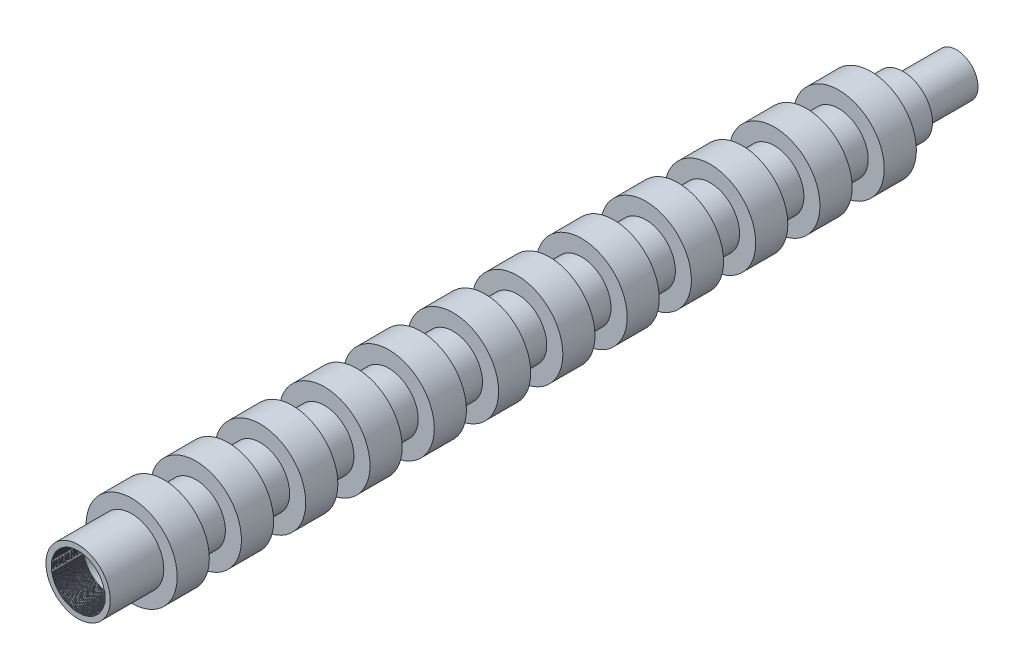
SolidWorks part; units mm, degrees
ref_plane "Front Plane" through (0, 0, 0) normal (0, 0, 1) x (1, 0, 0)
ref_plane "Top Plane" through (0, 0, 0) normal (0, 1, 0) x (1, 0, 0)
ref_plane "Right Plane" through (0, 0, 0) normal (1, 0, 0) x (0, 0, -1)
sketch "Sketch1" plane through (0, 0, 0) normal (0, 0, 1) x (1, 0, 0)
  circle A0 centre (0, 0) radius 6
  circle A1 centre (0, 0) radius 8.5
  dimension "D1" = 12
  dimension "D2" = 17
extrude "Boss-Extrude1" add sketch "Sketch1" along normal blind 10 contours A0 region at (0, 0, 0)
extrude "Boss-Extrude2" add sketch "Sketch1<3>" against normal blind 144 separate body contours A1 A0 | A0 region at (-8.2596, 0, 0)
sketch "Sketch1<3>" plane through (0, 0, 0) normal (0, 0, 1) x (1, 0, 0) same geometry as "Sketch1"
sketch "Sketch3" plane through (0, 0, 0) normal (0, 0, 1) x (1, 0, 0)
  circle A1 centre (0, 0) radius 8.5 construction
  circle A2 centre (0, 0) radius 8.5
sketch "Sketch4" plane through (0, 0, 0) normal (1, 0, 0) x (0, 0, -1)
  line L1 (6, 11.5) -> (12, 11.5)
  line L3 (6, 5.5) -> (12, 5.5)
  line L4 (12, 11.5) -> (12, 5.5)
  line L6 (6, 8.5) -> (12, 8.5) construction
  line L9 (6, 11.5) -> (6, 5.5)
  line L10 (0, 8.5) -> (0, -8.5) construction
  dimension "D1" = 6
  dimension "D2" = 6
  dimension "D3" = 6
sweep "Cut-Sweep1" cut profiles "Sketch4" path "Sketch3"
pattern_linear "LPattern1" count 12 spacing 12 along (0, 0, -1) of "Cut-Sweep1"
sketch "Sketch7" plane through (0, 0, 10) normal (0, 0, 1) x (1, 0, 0)
  line L1 (-5, 1) -> (5, 1)
  line L2 (-5, 1) -> (-5, -1)
  line L3 (-5, -1) -> (5, -1)
  line L4 (5, 1) -> (5, -1)
  line L5 (-5, 1) -> (5, -1) construction
  line L6 (-5, -1) -> (5, 1) construction
  circle A0 centre (0, 0) radius 5
  circle A3 centre (0, 0) radius 6 construction
  dimension "D1" = 10
  dimension "D2" = 1
  dimension "D3" = 2
extrude "Cut-Extrude1" cut sketch "Sketch7" against normal blind 10 contours L3 A0 | L1 A0 L3 | L1 A0 | L4 L3 L2 L1 region at (0, 2.6718, 10) region at (0, 0, 10) region at (0, -2.6718, 10)
sketch "Sketch10" plane through (0, 0, 10) normal (0, 0, 1) x (1, 0, 0)
  circle A0 centre (0, 0) radius 5
  dimension "D1" = 10
curve "Helix/Spiral2" pitch 0.225 height 6 radius 5 centre (0, 0, 10) axis (0, 0, -1) start towards (1, 0, 0)
sketch "Sketch12" plane through (0, 0, 0) normal (1, 0, 0) x (0, 0, -1)
  circle A0 centre (-9.9438, -5) radius 0.05
  spline S0 degree 3 poles (-10, 0) (-9.9953, -0.6513) (-9.9859, -1.9682) (-9.9718, -3.6318) (-9.9577, -4.7438) (-9.9437, -5.1305) (-9.9296, -4.734) (-9.9155, -3.6145) (-9.9014, -1.943) (-9.8873, 0.0252) (-9.8732, 1.9896) (-9.8592, 3.6501) (-9.8451, 4.7532) (-9.831, 5.1304) (-9.8169, 4.7242) (-9.8028, 3.5965) (-9.7887, 1.9196) (-9.7746, -0.0504) (-9.7606, -2.0128) (-9.7465, -3.6678) (-9.7324, -4.7626) (-9.7183, -5.1302) (-9.7042, -4.7143) (-9.6901, -3.5785) (-9.6761, -1.8962) (-9.662, 0.0757) (-9.6479, 2.036) (-9.6338, 3.6854) (-9.6197, 4.772) (-9.6056, 5.1298) (-9.5915, 4.7043) (-9.5775, 3.5604) (-9.5634, 1.8727) (-9.5493, -0.1009) (-9.5352, -2.0591) (-9.5211, -3.7029) (-9.507, -4.7812) (-9.493, -5.1293) (-9.4789, -4.6942) (-9.4648, -3.5422) (-9.4507, -1.8492) (-9.4366, 0.1261) (-9.4225, 2.0822) (-9.4085, 3.7203) (-9.3944, 4.7903) (-9.3803, 5.1287) (-9.3662, 4.6839) (-9.3521, 3.5239) (-9.338, 1.8257) (-9.3239, -0.1513) (-9.3099, -2.1052) (-9.2958, -3.7376) (-9.2817, -4.7992) (-9.2676, -5.128) (-9.2535, -4.6736) (-9.2394, -3.5055) (-9.2254, -1.8021) (-9.2113, 0.1765) (-9.1972, 2.1282) (-9.1831, 3.7549) (-9.169, 4.8081) (-9.1549, 5.1271) (-9.1408, 4.6631) (-9.1268, 3.487) (-9.1127, 1.7784) (-9.0986, -0.2017) (-9.0845, -2.1511) (-9.0704, -3.772) (-9.0563, -4.8168) (-9.0423, -5.1261) (-9.0282, -4.6525) (-9.0141, -3.4685) (-9, -1.7548) (-8.9859, 0.2269) (-8.9718, 2.174) (-8.9577, 3.789) (-8.9437, 4.8255) (-8.9296, 5.125) (-8.9155, 4.6419) (-8.9014, 3.4499) (-8.8873, 1.731) (-8.8732, -0.2521) (-8.8592, -2.1968) (-8.8451, -3.806) (-8.831, -4.834) (-8.8169, -5.1237) (-8.8028, -4.6311) (-8.7887, -3.4312) (-8.7746, -1.7073) (-8.7606, 0.2773) (-8.7465, 2.2196) (-8.7324, 3.8229) (-8.7183, 4.8424) (-8.7042, 5.1224) (-8.6901, 4.6201) (-8.6761, 3.4124) (-8.662, 1.6835) (-8.6479, -0.3025) (-8.6338, -2.2423) (-8.6197, -3.8397) (-8.6056, -4.8507) (-8.5915, -5.1209) (-8.5775, -4.6091) (-8.5634, -3.3935) (-8.5493, -1.6596) (-8.5352, 0.3277) (-8.5211, 2.265) (-8.507, 3.8563) (-8.493, 4.8588) (-8.4789, 5.1193) (-8.4648, 4.598) (-8.4507, 3.3745) (-8.4366, 1.6357) (-8.4225, -0.3529) (-8.4085, -2.2876) (-8.3944, -3.8729) (-8.3803, -4.8669) (-8.3662, -5.1176) (-8.3521, -4.5867) (-8.338, -3.3555) (-8.3239, -1.6118) (-8.3099, 0.378) (-8.2958, 2.3101) (-8.2817, 3.8894) (-8.2676, 4.8748) (-8.2535, 5.1157) (-8.2394, 4.5754) (-8.2254, 3.3364) (-8.2113, 1.5878) (-8.1972, -0.4032) (-8.1831, -2.3326) (-8.169, -3.9058) (-8.1549, -4.8826) (-8.1408, -5.1137) (-8.1268, -4.5639) (-8.1127, -3.3172) (-8.0986, -1.5638) (-8.0845, 0.4283) (-8.0704, 2.355) (-8.0563, 3.9221) (-8.0423, 4.8903) (-8.0282, 5.1116) (-8.0141, 4.5523) (-8, 3.2979) (-7.9859, 1.5398) (-7.9718, -0.4534) (-7.9577, -2.3774) (-7.9437, -3.9383) (-7.9296, -4.8978) (-7.9155, -5.1094) (-7.9014, -4.5406) (-7.8873, -3.2785) (-7.8732, -1.5157) (-7.8592, 0.4786) (-7.8451, 2.3997) (-7.831, 3.9545) (-7.8169, 4.9053) (-7.8028, 5.107) (-7.7887, 4.5289) (-7.7746, 3.2591) (-7.7606, 1.4916) (-7.7465, -0.5037) (-7.7324, -2.422) (-7.7183, -3.9705) (-7.7042, -4.9126) (-7.6901, -5.1045) (-7.6761, -4.5169) (-7.662, -3.2396) (-7.6479, -1.4674) (-7.6338, 0.5288) (-7.6197, 2.4442) (-7.6056, 3.9864) (-7.5915, 4.9198) (-7.5775, 5.1019) (-7.5634, 4.5049) (-7.5493, 3.22) (-7.5352, 1.4433) (-7.5211, -0.5538) (-7.507, -2.4664) (-7.493, -4.0022) (-7.4789, -4.9269) (-7.4648, -5.0992) (-7.4507, -4.4928) (-7.4366, -3.2003) (-7.4225, -1.419) (-7.4085, 0.5789) (-7.3944, 2.4885) (-7.3803, 4.018) (-7.3662, 4.9339) (-7.3521, 5.0964) (-7.338, 4.4806) (-7.3239, 3.1805) (-7.3099, 1.3948) (-7.2958, -0.604) (-7.2817, -2.5105) (-7.2676, -4.0336) (-7.2535, -4.9408) (-7.2394, -5.0934) (-7.2254, -4.4682) (-7.2113, -3.1607) (-7.1972, -1.3705) (-7.1831, 0.629) (-7.169, 2.5325) (-7.1549, 4.0492) (-7.1408, 4.9475) (-7.1268, 5.0903) (-7.1127, 4.4558) (-7.0986, 3.1408) (-7.0845, 1.3462) (-7.0704, -0.654) (-7.0563, -2.5544) (-7.0423, -4.0646) (-7.0282, -4.9541) (-7.0141, -5.0871) (-7, -4.4432) (-6.9859, -3.1208) (-6.9718, -1.3218) (-6.9577, 0.6791) (-6.9437, 2.5762) (-6.9296, 4.0799) (-6.9155, 4.9606) (-6.9014, 5.0838) (-6.8873, 4.4305) (-6.8732, 3.1007) (-6.8592, 1.2974) (-6.8451, -0.704) (-6.831, -2.598) (-6.8169, -4.0952) (-6.8028, -4.967) (-6.7887, -5.0803) (-6.7746, -4.4178) (-6.7606, -3.0806) (-6.7465, -1.273) (-6.7324, 0.729) (-6.7183, 2.6197) (-6.7042, 4.1103) (-6.6901, 4.9733) (-6.6761, 5.0767) (-6.662, 4.4049) (-6.6479, 3.0604) (-6.6338, 1.2485) (-6.6197, -0.754) (-6.6056, -2.6414) (-6.5915, -4.1254) (-6.5775, -4.9794) (-6.5634, -5.073) (-6.5493, -4.3919) (-6.5352, -3.0401) (-6.5211, -1.2241) (-6.507, 0.7789) (-6.493, 2.663) (-6.4789, 4.1403) (-6.4648, 4.9854) (-6.4507, 5.0692) (-6.4366, 4.3788) (-6.4225, 3.0198) (-6.4085, 1.1996) (-6.3944, -0.8038) (-6.3803, -2.6845) (-6.3662, -4.1552) (-6.3521, -4.9913) (-6.338, -5.0652) (-6.3239, -4.3656) (-6.3099, -2.9993) (-6.2958, -1.175) (-6.2817, 0.8287) (-6.2676, 2.7059) (-6.2535, 4.1699) (-6.2394, 4.9971) (-6.2254, 5.0612) (-6.2113, 4.3523) (-6.1972, 2.9788) (-6.1831, 1.1504) (-6.169, -0.8536) (-6.1549, -2.7273) (-6.1408, -4.1846) (-6.1268, -5.0027) (-6.1127, -5.057) (-6.0986, -4.3389) (-6.0845, -2.9583) (-6.0704, -1.1258) (-6.0563, 0.8785) (-6.0423, 2.7487) (-6.0282, 4.1991) (-6.0141, 5.0083) (-6, 5.0526) (-5.9859, 4.3254) (-5.9718, 2.9376) (-5.9577, 1.1012) (-5.9437, -0.9033) (-5.9296, -2.7699) (-5.9155, -4.2136) (-5.9014, -5.0137) (-5.8873, -5.0482) (-5.8732, -4.3118) (-5.8592, -2.9169) (-5.8451, -1.0766) (-5.831, 0.9282) (-5.8169, 2.7911) (-5.8028, 4.2279) (-5.7887, 5.019) (-5.7746, 5.0436) (-5.7606, 4.2981) (-5.7465, 2.8961) (-5.7324, 1.0519) (-5.7183, -0.9529) (-5.7042, -2.8123) (-5.6901, -4.2421) (-5.6761, -5.0242) (-5.662, -5.0389) (-5.6479, -4.2842) (-5.6338, -2.8753) (-5.6197, -1.0272) (-5.6056, 0.9777) (-5.5915, 2.8333) (-5.5775, 4.2563) (-5.5634, 5.0292) (-5.5493, 5.0341) (-5.5352, 4.2703) (-5.5211, 2.8543) (-5.507, 1.0025) (-5.493, -1.0025) (-5.4789, -2.8543) (-5.4648, -4.2703) (-5.4507, -5.0341) (-5.4366, -5.0292) (-5.4225, -4.2563) (-5.4085, -2.8333) (-5.3944, -0.9777) (-5.3803, 1.0272) (-5.3662, 2.8753) (-5.3521, 4.2842) (-5.338, 5.0389) (-5.3239, 5.0242) (-5.3099, 4.2421) (-5.2958, 2.8123) (-5.2817, 0.9529) (-5.2676, -1.0519) (-5.2535, -2.8961) (-5.2394, -4.2981) (-5.2254, -5.0436) (-5.2113, -5.019) (-5.1972, -4.2279) (-5.1831, -2.7911) (-5.169, -0.9282) (-5.1549, 1.0766) (-5.1408, 2.9169) (-5.1268, 4.3118) (-5.1127, 5.0482) (-5.0986, 5.0137) (-5.0845, 4.2136) (-5.0704, 2.7699) (-5.0563, 0.9033) (-5.0423, -1.1012) (-5.0282, -2.9376) (-5.0141, -4.3254) (-5, -5.0526) (-4.9859, -5.0083) (-4.9718, -4.1991) (-4.9577, -2.7487) (-4.9437, -0.8785) (-4.9296, 1.1258) (-4.9155, 2.9583) (-4.9014, 4.3389) (-4.8873, 5.057) (-4.8732, 5.0027) (-4.8592, 4.1846) (-4.8451, 2.7273) (-4.831, 0.8536) (-4.8169, -1.1504) (-4.8028, -2.9788) (-4.7887, -4.3523) (-4.7746, -5.0612) (-4.7606, -4.9971) (-4.7465, -4.1699) (-4.7324, -2.7059) (-4.7183, -0.8287) (-4.7042, 1.175) (-4.6901, 2.9993) (-4.6761, 4.3656) (-4.662, 5.0652) (-4.6479, 4.9913) (-4.6338, 4.1552) (-4.6197, 2.6845) (-4.6056, 0.8038) (-4.5915, -1.1996) (-4.5775, -3.0198) (-4.5634, -4.3788) (-4.5493, -5.0692) (-4.5352, -4.9854) (-4.5211, -4.1403) (-4.507, -2.663) (-4.493, -0.7789) (-4.4789, 1.2241) (-4.4648, 3.0401) (-4.4507, 4.3919) (-4.4366, 5.073) (-4.4225, 4.9794) (-4.4085, 4.1254) (-4.3944, 2.6414) (-4.3803, 0.754) (-4.3662, -1.2485) (-4.3521, -3.0604) (-4.338, -4.4049) (-4.3239, -5.0767) (-4.3099, -4.9733) (-4.2958, -4.1103) (-4.2817, -2.6197) (-4.2676, -0.729) (-4.2535, 1.273) (-4.2394, 3.0806) (-4.2254, 4.4178) (-4.2113, 5.0803) (-4.1972, 4.967) (-4.1831, 4.0952) (-4.169, 2.598) (-4.1549, 0.704) (-4.1408, -1.2974) (-4.1268, -3.1007) (-4.1127, -4.4305) (-4.0986, -5.0838) (-4.0845, -4.9606) (-4.0704, -4.0799) (-4.0563, -2.5762) (-4.0423, -0.6791) (-4.0282, 1.3221) (-4.0141, 3.1198) (-4.0047, 4.0045) (-4, 4.3301) knots 0 0 0 0 0.002347 0.004695 0.007042 0.00939 0.011737 0.014085 0.016432 0.018779 0.021127 0.023474 0.025822 0.028169 0.030516 0.032864 0.035211 0.037559 0.039906 0.042254 0.044601 0.046948 0.049296 0.051643 0.053991 0.056338 0.058685 0.061033 0.06338 0.065728 0.068075 0.070423 0.07277 0.075117 0.077465 0.079812 0.08216 0.084507 0.086854 0.089202 0.091549 0.093897 0.096244 0.098592 0.100939 0.103286 0.105634 0.107981 0.110329 0.112676 0.115023 0.117371 0.119718 0.122066 0.124413 0.126761 0.129108 0.131455 0.133803 0.13615 0.138498 0.140845 0.143192 0.14554 0.147887 0.150235 0.152582 0.15493 0.157277 0.159624 0.161972 0.164319 0.166667 0.169014 0.171362 0.173709 0.176056 0.178404 0.180751 0.183099 0.185446 0.187793 0.190141 0.192488 0.194836 0.197183 0.199531 0.201878 0.204225 0.206573 0.20892 0.211268 0.213615 0.215962 0.21831 0.220657 0.223005 0.225352 0.2277 0.230047 0.232394 0.234742 0.237089 0.239437 0.241784 0.244131 0.246479 0.248826 0.251174 0.253521 0.255869 0.258216 0.260563 0.262911 0.265258 0.267606 0.269953 0.2723 0.274648 0.276995 0.279343 0.28169 0.284038 0.286385 0.288732 0.29108 0.293427 0.295775 0.298122 0.300469 0.302817 0.305164 0.307512 0.309859 0.312207 0.314554 0.316901 0.319249 0.321596 0.323944 0.326291 0.328638 0.330986 0.333333 0.335681 0.338028 0.340376 0.342723 0.34507 0.347418 0.349765 0.352113 0.35446 0.356808 0.359155 0.361502 0.36385 0.366197 0.368545 0.370892 0.373239 0.375587 0.377934 0.380282 0.382629 0.384977 0.387324 0.389671 0.392019 0.394366 0.396714 0.399061 0.401408 0.403756 0.406103 0.408451 0.410798 0.413146 0.415493 0.41784 0.420188 0.422535 0.424883 0.42723 0.429577 0.431925 0.434272 0.43662 0.438967 0.441315 0.443662 0.446009 0.448357 0.450704 0.453052 0.455399 0.457746 0.460094 0.462441 0.464789 0.467136 0.469484 0.471831 0.474178 0.476526 0.478873 0.481221 0.483568 0.485915 0.488263 0.49061 0.492958 0.495305 0.497653 0.5 0.502347 0.504695 0.507042 0.50939 0.511737 0.514085 0.516432 0.518779 0.521127 0.523474 0.525822 0.528169 0.530516 0.532864 0.535211 0.537559 0.539906 0.542254 0.544601 0.546948 0.549296 0.551643 0.553991 0.556338 0.558685 0.561033 0.56338 0.565728 0.568075 0.570423 0.57277 0.575117 0.577465 0.579812 0.58216 0.584507 0.586854 0.589202 0.591549 0.593897 0.596244 0.598592 0.600939 0.603286 0.605634 0.607981 0.610329 0.612676 0.615023 0.617371 0.619718 0.622066 0.624413 0.626761 0.629108 0.631455 0.633803 0.63615 0.638498 0.640845 0.643192 0.64554 0.647887 0.650235 0.652582 0.65493 0.657277 0.659624 0.661972 0.664319 0.666667 0.669014 0.671362 0.673709 0.676056 0.678404 0.680751 0.683099 0.685446 0.687793 0.690141 0.692488 0.694836 0.697183 0.699531 0.701878 0.704225 0.706573 0.70892 0.711268 0.713615 0.715962 0.71831 0.720657 0.723005 0.725352 0.7277 0.730047 0.732394 0.734742 0.737089 0.739437 0.741784 0.744131 0.746479 0.748826 0.751174 0.753521 0.755869 0.758216 0.760563 0.762911 0.765258 0.767606 0.769953 0.7723 0.774648 0.776995 0.779343 0.78169 0.784038 0.786385 0.788732 0.79108 0.793427 0.795775 0.798122 0.800469 0.802817 0.805164 0.807512 0.809859 0.812207 0.814554 0.816901 0.819249 0.821596 0.823944 0.826291 0.828638 0.830986 0.833333 0.835681 0.838028 0.840376 0.842723 0.84507 0.847418 0.849765 0.852113 0.85446 0.856808 0.859155 0.861502 0.86385 0.866197 0.868545 0.870892 0.873239 0.875587 0.877934 0.880282 0.882629 0.884977 0.887324 0.889671 0.892019 0.894366 0.896714 0.899061 0.901408 0.903756 0.906103 0.908451 0.910798 0.913146 0.915493 0.91784 0.920188 0.922535 0.924883 0.92723 0.929577 0.931925 0.934272 0.93662 0.938967 0.941315 0.943662 0.946009 0.948357 0.950704 0.953052 0.955399 0.957746 0.960094 0.962441 0.964789 0.967136 0.969484 0.971831 0.974178 0.976526 0.978873 0.981221 0.983568 0.985915 0.988263 0.99061 0.992958 0.995305 0.997653 1 1 1 1 construction
  dimension "D1" = 0.1
sweep "Cut-Sweep4" cut profiles "Sketch12" path "Helix/Spiral2"
sketch "Sketch13" plane through (0, 0, -144) normal (0, 0, -1) x (-1, 0, 0)
  circle A2 centre (0, 0) radius 4
  dimension "D1" = 8
extrude "Boss-Extrude3" add sketch "Sketch13" along normal blind 10
